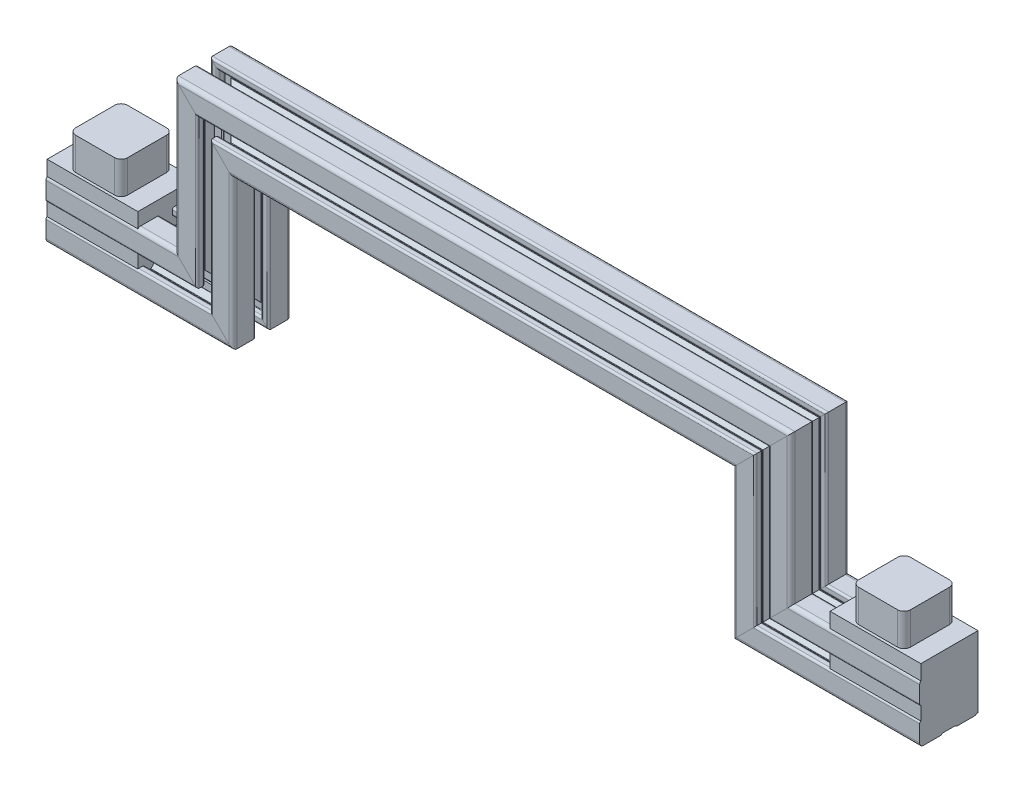
SolidWorks part; units mm, degrees
material "Commercially Pure CP-Ti UNS R50400 (SS)"
ref_plane "Front Plane" through (0, 0, 0) normal (0, 0, 1) x (1, 0, 0)
ref_plane "Top Plane" through (0, 0, 0) normal (0, 1, 0) x (1, 0, 0)
ref_plane "Right Plane" through (0, 0, 0) normal (1, 0, 0) x (0, 0, -1)
sketch "Sketch7" plane through (0, 0, 0) normal (1, 0, 0) x (0, 0, -1)
  line L0 (13.9698, 21.2743) -> (13.5298, 21.2743)
  line L1 (12.0298, 22.7743) -> (12.0298, 23.2743)
  line L2 (13.5298, 24.7743) -> (23.1398, 24.7743)
  line L3 (25.4198, 22.4943) -> (25.4198, 12.8843)
  line L4 (23.9198, 11.3843) -> (23.4198, 11.3843)
  line L5 (21.9198, 12.8843) -> (21.9198, 13.3243)
  line L6 (20.9198, 14.3243) -> (15.3498, 14.3243)
  line L7 (14.9698, 14.7043) -> (14.9698, 20.2743)
  line L8 (21.9589, -6.6897) -> (21.9589, -6.2497)
  line L9 (23.4589, -4.7497) -> (23.9589, -4.7497)
  line L10 (25.4589, -6.2497) -> (25.4589, -15.8597)
  line L11 (23.1789, -18.1397) -> (13.5689, -18.1397)
  line L12 (12.0689, -16.6397) -> (12.0689, -16.1397)
  line L13 (13.5689, -14.6397) -> (14.0089, -14.6397)
  line L14 (15.0089, -13.6397) -> (15.0089, -8.0697)
  line L15 (15.3889, -7.6897) -> (20.9589, -7.6897)
  line L16 (-6.0052, -14.6787) -> (-5.5652, -14.6787)
  line L17 (-4.0652, -16.1787) -> (-4.0652, -16.6787)
  line L18 (-5.5652, -18.1787) -> (-15.1752, -18.1787)
  line L19 (-17.4552, -15.8987) -> (-17.4552, -6.2887)
  line L20 (-15.9552, -4.7887) -> (-15.4552, -4.7887)
  line L21 (-13.9552, -6.2887) -> (-13.9552, -6.7287)
  line L22 (-12.9552, -7.7287) -> (-7.3852, -7.7287)
  line L23 (-7.0052, -8.1087) -> (-7.0052, -13.6787)
  line L24 (1.8289, -2.4886) -> (1.4132, -2.3164)
  line L25 (-1.632, 0.7289) -> (-1.8042, 1.1447)
  line L26 (-1.804, 5.4512) -> (-1.6318, 5.867)
  line L27 (1.4134, 8.9121) -> (1.8292, 9.0843)
  line L28 (6.1358, 9.0842) -> (6.5515, 8.912)
  line L29 (9.5966, 5.8667) -> (9.7688, 5.451)
  line L30 (9.7687, 1.1444) -> (9.5965, 0.7287)
  line L31 (6.5512, -2.3165) -> (6.1355, -2.4887)
  line L32 (-13.9942, 13.2853) -> (-13.9942, 12.8453)
  line L33 (-15.4942, 11.3453) -> (-15.9942, 11.3453)
  line L34 (-17.4942, 12.8453) -> (-17.4942, 22.4553)
  line L35 (-15.2142, 24.7353) -> (-5.6042, 24.7353)
  line L36 (-4.1042, 23.2353) -> (-4.1042, 22.7353)
  line L37 (-5.6042, 21.2353) -> (-6.0442, 21.2353)
  line L38 (-7.0442, 20.2353) -> (-7.0442, 14.6653)
  line L39 (-7.4242, 14.2853) -> (-12.9942, 14.2853)
  line L40 (4.9058, 11.2153) -> (4.0058, 10.7002)
  line L41 (4.0058, 10.7002) -> (3.1058, 11.2153)
  line L42 (3.1058, 11.2153) -> (-2.1975, 11.2153)
  line L43 (-2.4662, 11.3266) -> (-5.9329, 14.7933)
  line L44 (-6.0442, 15.062) -> (-6.0442, 19.3553)
  line L45 (-5.6642, 19.7353) -> (-2.5792, 19.7353)
  line L46 (-1.0592, 21.2553) -> (-1.0592, 24.2153)
  line L47 (-2.5792, 25.7353) -> (-15.4942, 25.7353)
  line L48 (-18.4942, 22.7353) -> (-18.4942, 9.8203)
  line L49 (-16.9742, 8.3003) -> (-14.0142, 8.3003)
  line L50 (-12.4942, 9.8203) -> (-12.4942, 12.9053)
  line L51 (-12.1142, 13.2853) -> (-7.8138, 13.2853)
  line L52 (-7.5451, 13.174) -> (-4.0855, 9.7144)
  line L53 (-3.9742, 9.4457) -> (-3.9742, 4.1353)
  line L54 (-3.9742, 4.1353) -> (-3.4546, 3.2353)
  line L55 (-3.4546, 3.2353) -> (-3.9742, 2.3353)
  line L56 (-3.9742, 2.3353) -> (-3.9742, -2.968)
  line L57 (-4.0855, -3.2367) -> (-7.5522, -6.7034)
  line L58 (-7.8209, -6.8147) -> (-12.1142, -6.8147)
  line L59 (-12.4942, -6.4347) -> (-12.4942, -3.3497)
  line L60 (-14.0142, -1.8297) -> (-16.9742, -1.8297)
  line L61 (-18.4942, -3.3497) -> (-18.4942, -16.2647)
  line L62 (-15.4942, -19.2647) -> (-2.5792, -19.2647)
  line L63 (-1.0592, -17.7447) -> (-1.0592, -14.7847)
  line L64 (-2.5792, -13.2647) -> (-5.6642, -13.2647)
  line L65 (-6.0442, -12.8847) -> (-6.0442, -8.5843)
  line L66 (-5.9329, -8.3156) -> (-2.4733, -4.856)
  line L67 (-2.2046, -4.7447) -> (3.1058, -4.7447)
  line L68 (3.1058, -4.7447) -> (4.0058, -4.2295)
  line L69 (4.0058, -4.2295) -> (4.9058, -4.7447)
  line L70 (4.9058, -4.7447) -> (10.2091, -4.7447)
  line L71 (10.4778, -4.856) -> (13.9445, -8.3227)
  line L72 (14.0558, -8.5914) -> (14.0558, -12.8847)
  line L73 (13.6758, -13.2647) -> (10.5908, -13.2647)
  line L74 (9.0708, -14.7847) -> (9.0708, -17.7447)
  line L75 (10.5908, -19.2647) -> (23.5058, -19.2647)
  line L76 (26.5058, -16.2647) -> (26.5058, -3.3497)
  line L77 (24.9858, -1.8297) -> (22.0258, -1.8297)
  line L78 (20.5058, -3.3497) -> (20.5058, -6.4347)
  line L79 (20.1258, -6.8147) -> (15.8254, -6.8147)
  line L80 (15.5567, -6.7034) -> (12.0971, -3.2438)
  line L81 (11.9858, -2.9751) -> (11.9858, 2.3353)
  line L82 (11.9858, 2.3353) -> (11.4662, 3.2353)
  line L83 (11.4662, 3.2353) -> (11.9858, 4.1353)
  line L84 (11.9858, 4.1353) -> (11.9858, 9.4386)
  line L85 (12.0971, 9.7073) -> (15.5638, 13.174)
  line L86 (15.8325, 13.2853) -> (20.1258, 13.2853)
  line L87 (20.5058, 12.9053) -> (20.5058, 9.8203)
  line L88 (22.0258, 8.3003) -> (24.9858, 8.3003)
  line L89 (26.5058, 9.8203) -> (26.5058, 22.7353)
  line L90 (23.5058, 25.7353) -> (10.5908, 25.7353)
  line L91 (9.0708, 24.2153) -> (9.0708, 21.2553)
  line L92 (10.5908, 19.7353) -> (13.6758, 19.7353)
  line L93 (14.0558, 19.3553) -> (14.0558, 15.0549)
  line L94 (13.9445, 14.7862) -> (10.4849, 11.3266)
  line L95 (10.2162, 11.2153) -> (4.9058, 11.2153)
  arc A0 (14.9698, 20.2743) -> (13.9698, 21.2743) centre (13.9698, 20.2743) ccw
  arc A1 (12.0298, 22.7743) -> (13.5298, 21.2743) centre (13.5298, 22.7743) ccw
  arc A2 (13.5298, 24.7743) -> (12.0298, 23.2743) centre (13.5298, 23.2743) ccw
  arc A3 (25.4198, 22.4943) -> (23.1398, 24.7743) centre (23.1398, 22.4943) ccw
  arc A4 (23.9198, 11.3843) -> (25.4198, 12.8843) centre (23.9198, 12.8843) ccw
  arc A5 (21.9198, 12.8843) -> (23.4198, 11.3843) centre (23.4198, 12.8843) ccw
  arc A6 (21.9198, 13.3243) -> (20.9198, 14.3243) centre (20.9198, 13.3243) ccw
  arc A7 (14.9698, 14.7043) -> (15.3498, 14.3243) centre (15.3498, 14.7043) ccw
  arc A8 (20.9589, -7.6897) -> (21.9589, -6.6897) centre (20.9589, -6.6897) ccw
  arc A9 (23.4589, -4.7497) -> (21.9589, -6.2497) centre (23.4589, -6.2497) ccw
  arc A10 (25.4589, -6.2497) -> (23.9589, -4.7497) centre (23.9589, -6.2497) ccw
  arc A11 (23.1789, -18.1397) -> (25.4589, -15.8597) centre (23.1789, -15.8597) ccw
  arc A12 (12.0689, -16.6397) -> (13.5689, -18.1397) centre (13.5689, -16.6397) ccw
  arc A13 (13.5689, -14.6397) -> (12.0689, -16.1397) centre (13.5689, -16.1397) ccw
  arc A14 (14.0089, -14.6397) -> (15.0089, -13.6397) centre (14.0089, -13.6397) ccw
  arc A15 (15.3889, -7.6897) -> (15.0089, -8.0697) centre (15.3889, -8.0697) ccw
  arc A16 (-7.0052, -13.6787) -> (-6.0052, -14.6787) centre (-6.0052, -13.6787) ccw
  arc A17 (-4.0652, -16.1787) -> (-5.5652, -14.6787) centre (-5.5652, -16.1787) ccw
  arc A18 (-5.5652, -18.1787) -> (-4.0652, -16.6787) centre (-5.5652, -16.6787) ccw
  arc A19 (-17.4552, -15.8987) -> (-15.1752, -18.1787) centre (-15.1752, -15.8987) ccw
  arc A20 (-15.9552, -4.7887) -> (-17.4552, -6.2887) centre (-15.9552, -6.2887) ccw
  arc A21 (-13.9552, -6.2887) -> (-15.4552, -4.7887) centre (-15.4552, -6.2887) ccw
  arc A22 (-13.9552, -6.7287) -> (-12.9552, -7.7287) centre (-12.9552, -6.7287) ccw
  arc A23 (-7.0052, -8.1087) -> (-7.3852, -7.7287) centre (-7.3852, -8.1087) ccw
  arc A24 (1.0363, -0.7421) -> (1.4132, -2.3164) centre (1.7959, -1.3925) ccw
  arc A25 (-0.0577, 0.352) -> (1.0363, -0.7421) centre (3.9823, 3.2978) ccw
  arc A26 (-1.632, 0.7289) -> (-0.0577, 0.352) centre (-0.7081, 1.1116) ccw
  arc A27 (-0.9575, 2.5244) -> (-1.8042, 1.1447) centre (-0.8803, 1.5274) ccw
  arc A28 (-0.9574, 4.0715) -> (-0.9575, 2.5244) centre (3.9823, 3.2978) ccw
  arc A29 (-1.804, 5.4512) -> (-0.9574, 4.0715) centre (-0.8802, 5.0686) ccw
  arc A30 (-0.0575, 6.2439) -> (-1.6318, 5.867) centre (-0.708, 5.4843) ccw
  arc A31 (1.0365, 7.3379) -> (-0.0575, 6.2439) centre (3.9823, 3.2978) ccw
  arc A32 (1.4134, 8.9121) -> (1.0365, 7.3379) centre (1.7961, 7.9882) ccw
  arc A33 (3.2089, 8.2376) -> (1.8292, 9.0843) centre (2.2119, 8.1604) ccw
  arc A34 (4.7561, 8.2376) -> (3.2089, 8.2376) centre (3.9823, 3.2978) ccw
  arc A35 (6.1358, 9.0842) -> (4.7561, 8.2376) centre (5.7531, 8.1603) ccw
  arc A36 (6.9284, 7.3377) -> (6.5515, 8.912) centre (6.1688, 7.9881) ccw
  arc A37 (8.0224, 6.2437) -> (6.9284, 7.3377) centre (3.9823, 3.2978) ccw
  arc A38 (9.5966, 5.8667) -> (8.0224, 6.2437) centre (8.6727, 5.484) ccw
  arc A39 (8.9222, 4.0713) -> (9.7688, 5.451) centre (8.845, 5.0683) ccw
  arc A40 (8.9221, 2.5241) -> (8.9222, 4.0713) centre (3.9823, 3.2978) ccw
  arc A41 (9.7687, 1.1444) -> (8.9221, 2.5241) centre (8.8448, 1.5271) ccw
  arc A42 (8.0222, 0.3518) -> (9.5965, 0.7287) centre (8.6726, 1.1113) ccw
  arc A43 (6.9282, -0.7422) -> (8.0222, 0.3518) centre (3.9823, 3.2978) ccw
  arc A44 (6.5512, -2.3165) -> (6.9282, -0.7422) centre (6.1685, -1.3926) ccw
  arc A45 (4.7558, -1.642) -> (6.1355, -2.4887) centre (5.7528, -1.5648) ccw
  arc A46 (3.2086, -1.642) -> (4.7558, -1.642) centre (3.9823, 3.2978) ccw
  arc A47 (1.8289, -2.4886) -> (3.2086, -1.642) centre (2.2116, -1.5647) ccw
  arc A48 (-12.9942, 14.2853) -> (-13.9942, 13.2853) centre (-12.9942, 13.2853) ccw
  arc A49 (-15.4942, 11.3453) -> (-13.9942, 12.8453) centre (-15.4942, 12.8453) ccw
  arc A50 (-17.4942, 12.8453) -> (-15.9942, 11.3453) centre (-15.9942, 12.8453) ccw
  arc A51 (-15.2142, 24.7353) -> (-17.4942, 22.4553) centre (-15.2142, 22.4553) ccw
  arc A52 (-4.1042, 23.2353) -> (-5.6042, 24.7353) centre (-5.6042, 23.2353) ccw
  arc A53 (-5.6042, 21.2353) -> (-4.1042, 22.7353) centre (-5.6042, 22.7353) ccw
  arc A54 (-6.0442, 21.2353) -> (-7.0442, 20.2353) centre (-6.0442, 20.2353) ccw
  arc A55 (-7.4242, 14.2853) -> (-7.0442, 14.6653) centre (-7.4242, 14.6653) ccw
  arc A56 (-2.4662, 11.3266) -> (-2.1975, 11.2153) centre (-2.1975, 11.5953) ccw
  arc A57 (-6.0442, 15.062) -> (-5.9329, 14.7933) centre (-5.6642, 15.062) ccw
  arc A58 (-5.6642, 19.7353) -> (-6.0442, 19.3553) centre (-5.6642, 19.3553) ccw
  arc A59 (-2.5792, 19.7353) -> (-1.0592, 21.2553) centre (-2.5792, 21.2553) ccw
  arc A60 (-1.0592, 24.2153) -> (-2.5792, 25.7353) centre (-2.5792, 24.2153) ccw
  arc A61 (-15.4942, 25.7353) -> (-18.4942, 22.7353) centre (-15.4942, 22.7353) ccw
  arc A62 (-18.4942, 9.8203) -> (-16.9742, 8.3003) centre (-16.9742, 9.8203) ccw
  arc A63 (-14.0142, 8.3003) -> (-12.4942, 9.8203) centre (-14.0142, 9.8203) ccw
  arc A64 (-12.1142, 13.2853) -> (-12.4942, 12.9053) centre (-12.1142, 12.9053) ccw
  arc A65 (-7.5451, 13.174) -> (-7.8138, 13.2853) centre (-7.8138, 12.9053) ccw
  arc A66 (-3.9742, 9.4457) -> (-4.0855, 9.7144) centre (-4.3542, 9.4457) ccw
  arc A67 (-4.0855, -3.2367) -> (-3.9742, -2.968) centre (-4.3542, -2.968) ccw
  arc A68 (-7.8209, -6.8147) -> (-7.5522, -6.7034) centre (-7.8209, -6.4347) ccw
  arc A69 (-12.4942, -6.4347) -> (-12.1142, -6.8147) centre (-12.1142, -6.4347) ccw
  arc A70 (-12.4942, -3.3497) -> (-14.0142, -1.8297) centre (-14.0142, -3.3497) ccw
  arc A71 (-16.9742, -1.8297) -> (-18.4942, -3.3497) centre (-16.9742, -3.3497) ccw
  arc A72 (-18.4942, -16.2647) -> (-15.4942, -19.2647) centre (-15.4942, -16.2647) ccw
  arc A73 (-2.5792, -19.2647) -> (-1.0592, -17.7447) centre (-2.5792, -17.7447) ccw
  arc A74 (-1.0592, -14.7847) -> (-2.5792, -13.2647) centre (-2.5792, -14.7847) ccw
  arc A75 (-6.0442, -12.8847) -> (-5.6642, -13.2647) centre (-5.6642, -12.8847) ccw
  arc A76 (-5.9329, -8.3156) -> (-6.0442, -8.5843) centre (-5.6642, -8.5843) ccw
  arc A77 (-2.2046, -4.7447) -> (-2.4733, -4.856) centre (-2.2046, -5.1247) ccw
  arc A78 (10.4778, -4.856) -> (10.2091, -4.7447) centre (10.2091, -5.1247) ccw
  arc A79 (14.0558, -8.5914) -> (13.9445, -8.3227) centre (13.6758, -8.5914) ccw
  arc A80 (13.6758, -13.2647) -> (14.0558, -12.8847) centre (13.6758, -12.8847) ccw
  arc A81 (10.5908, -13.2647) -> (9.0708, -14.7847) centre (10.5908, -14.7847) ccw
  arc A82 (9.0708, -17.7447) -> (10.5908, -19.2647) centre (10.5908, -17.7447) ccw
  arc A83 (23.5058, -19.2647) -> (26.5058, -16.2647) centre (23.5058, -16.2647) ccw
  arc A84 (26.5058, -3.3497) -> (24.9858, -1.8297) centre (24.9858, -3.3497) ccw
  arc A85 (22.0258, -1.8297) -> (20.5058, -3.3497) centre (22.0258, -3.3497) ccw
  arc A86 (20.1258, -6.8147) -> (20.5058, -6.4347) centre (20.1258, -6.4347) ccw
  arc A87 (15.5567, -6.7034) -> (15.8254, -6.8147) centre (15.8254, -6.4347) ccw
  arc A88 (11.9858, -2.9751) -> (12.0971, -3.2438) centre (12.3658, -2.9751) ccw
  arc A89 (12.0971, 9.7073) -> (11.9858, 9.4386) centre (12.3658, 9.4386) ccw
  arc A90 (15.8325, 13.2853) -> (15.5638, 13.174) centre (15.8325, 12.9053) ccw
  arc A91 (20.5058, 12.9053) -> (20.1258, 13.2853) centre (20.1258, 12.9053) ccw
  arc A92 (20.5058, 9.8203) -> (22.0258, 8.3003) centre (22.0258, 9.8203) ccw
  arc A93 (24.9858, 8.3003) -> (26.5058, 9.8203) centre (24.9858, 9.8203) ccw
  arc A94 (26.5058, 22.7353) -> (23.5058, 25.7353) centre (23.5058, 22.7353) ccw
  arc A95 (10.5908, 25.7353) -> (9.0708, 24.2153) centre (10.5908, 24.2153) ccw
  arc A96 (9.0708, 21.2553) -> (10.5908, 19.7353) centre (10.5908, 21.2553) ccw
  arc A97 (14.0558, 19.3553) -> (13.6758, 19.7353) centre (13.6758, 19.3553) ccw
  arc A98 (13.9445, 14.7862) -> (14.0558, 15.0549) centre (13.6758, 15.0549) ccw
  arc A99 (10.2162, 11.2153) -> (10.4849, 11.3266) centre (10.2162, 11.5953) ccw
sketch "Sketch1" plane through (0, 0, 0) normal (0, 0, 1) x (1, 0, 0)
  line L0 (0, 0) -> (125, 0)
  line L1 (125, 0) -> (125, 115.0707)
  line L2 (125, 115.0707) -> (337, 115.0707)
  dimension "D1" = 337
  dimension "D2" = 125
sketch "Sketch2" [suppressed] plane through (0, 0, 0) normal (1, 0, 0) x (0, 0, -1)
  line L0 (-33.5, -41) -> (-31.5, -41)
  line L1 (-31.5, -43) -> (-42, -43)
  line L2 (-43, -42) -> (-43, -31.5)
  line L3 (-41, -31.5) -> (-41, -33.5)
  line L4 (-40, -34.5) -> (-34.88, -34.5)
  line L5 (-34.5, -34.88) -> (-34.5, -40)
  line L6 (-16.657, -26.2238) -> (-18.284, -25.188)
  line L7 (-19.8123, -26.7162) -> (-18.7764, -28.3429)
  line L8 (-21.0015, -29.2647) -> (-21.4195, -27.3819)
  line L9 (-23.5808, -27.3818) -> (-23.9986, -29.2645)
  line L10 (-26.2238, -28.343) -> (-25.188, -26.716)
  line L11 (-26.7162, -25.1877) -> (-28.3429, -26.2236)
  line L12 (-29.2647, -23.9985) -> (-27.3819, -23.5805)
  line L13 (-27.3818, -21.4192) -> (-29.2645, -21.0014)
  line L14 (-28.343, -18.7762) -> (-26.716, -19.812)
  line L15 (-25.1877, -18.2838) -> (-26.2236, -16.6571)
  line L16 (-23.9985, -15.7353) -> (-23.5805, -17.6181)
  line L17 (-21.4192, -17.6182) -> (-21.0014, -15.7355)
  line L18 (-18.7762, -16.657) -> (-19.812, -18.284)
  line L19 (-18.2838, -19.8123) -> (-16.6571, -18.7764)
  line L20 (-15.7353, -21.0015) -> (-17.6181, -21.4195)
  line L21 (-17.6182, -23.5808) -> (-15.7355, -23.9986)
  line L22 (41, -33.5) -> (41, -31.5)
  line L23 (43, -31.5) -> (43, -42)
  line L24 (42, -43) -> (31.5, -43)
  line L25 (31.5, -41) -> (33.5, -41)
  line L26 (34.5, -40) -> (34.5, -34.88)
  line L27 (34.88, -34.5) -> (40, -34.5)
  line L28 (26.7162, -19.8123) -> (28.3429, -18.7764)
  line L29 (29.2647, -21.0015) -> (27.3819, -21.4195)
  line L30 (27.3818, -23.5808) -> (29.2645, -23.9986)
  line L31 (28.343, -26.2238) -> (26.716, -25.188)
  line L32 (25.1877, -26.7162) -> (26.2236, -28.3429)
  line L33 (23.9985, -29.2647) -> (23.5805, -27.3819)
  line L34 (21.4192, -27.3818) -> (21.0014, -29.2645)
  line L35 (18.7762, -28.343) -> (19.812, -26.716)
  line L36 (18.2838, -25.1877) -> (16.6571, -26.2236)
  line L37 (15.7353, -23.9985) -> (17.6181, -23.5805)
  line L38 (17.6182, -21.4192) -> (15.7355, -21.0014)
  line L39 (16.657, -18.7762) -> (18.284, -19.812)
  line L40 (19.8123, -18.2838) -> (18.7764, -16.6571)
  line L41 (21.0015, -15.7353) -> (21.4195, -17.6181)
  line L42 (23.5808, -17.6182) -> (23.9986, -15.7355)
  line L43 (26.2238, -16.657) -> (25.188, -18.284)
  line L44 (34.5, 34.88) -> (34.5, 40)
  line L45 (33.5, 41) -> (31.5, 41)
  line L46 (31.5, 43) -> (42, 43)
  line L47 (43, 42) -> (43, 31.5)
  line L48 (41, 31.5) -> (41, 33.5)
  line L49 (40, 34.5) -> (34.88, 34.5)
  line L50 (26.7162, 25.1877) -> (28.3429, 26.2236)
  line L51 (29.2647, 23.9985) -> (27.3819, 23.5805)
  line L52 (27.3818, 21.4192) -> (29.2645, 21.0014)
  line L53 (28.343, 18.7762) -> (26.716, 19.812)
  line L54 (25.1877, 18.2838) -> (26.2236, 16.6571)
  line L55 (23.9985, 15.7353) -> (23.5805, 17.6181)
  line L56 (21.4192, 17.6182) -> (21.0014, 15.7355)
  line L57 (18.7762, 16.657) -> (19.812, 18.284)
  line L58 (18.2838, 19.8123) -> (16.6571, 18.7764)
  line L59 (15.7353, 21.0015) -> (17.6181, 21.4195)
  line L60 (17.6182, 23.5808) -> (15.7355, 23.9986)
  line L61 (16.657, 26.2238) -> (18.284, 25.188)
  line L62 (19.8123, 26.7162) -> (18.7764, 28.3429)
  line L63 (21.0015, 29.2647) -> (21.4195, 27.3819)
  line L64 (23.5808, 27.3818) -> (23.9986, 29.2645)
  line L65 (26.2238, 28.343) -> (25.188, 26.716)
  line L66 (-41, 33.5) -> (-41, 31.5)
  line L67 (-43, 31.5) -> (-43, 42)
  line L68 (-42, 43) -> (-31.5, 43)
  line L69 (-31.5, 41) -> (-33.5, 41)
  line L70 (-34.5, 40) -> (-34.5, 34.88)
  line L71 (-34.88, 34.5) -> (-40, 34.5)
  line L72 (-16.657, 18.7762) -> (-18.284, 19.812)
  line L73 (-19.8123, 18.2838) -> (-18.7764, 16.6571)
  line L74 (-21.0015, 15.7353) -> (-21.4195, 17.6181)
  line L75 (-23.5808, 17.6182) -> (-23.9986, 15.7355)
  line L76 (-26.2238, 16.657) -> (-25.188, 18.284)
  line L77 (-26.7162, 19.8123) -> (-28.3429, 18.7764)
  line L78 (-29.2647, 21.0015) -> (-27.3819, 21.4195)
  line L79 (-27.3818, 23.5808) -> (-29.2645, 23.9986)
  line L80 (-28.343, 26.2238) -> (-26.716, 25.188)
  line L81 (-25.1877, 26.7162) -> (-26.2236, 28.3429)
  line L82 (-23.9985, 29.2647) -> (-23.5805, 27.3819)
  line L83 (-21.4192, 27.3818) -> (-21.0014, 29.2645)
  line L84 (-18.7762, 28.343) -> (-19.812, 26.716)
  line L85 (-18.2838, 25.1877) -> (-16.6571, 26.2236)
  line L86 (-15.7353, 23.9985) -> (-17.6181, 23.5805)
  line L87 (-17.6182, 21.4192) -> (-15.7355, 21.0014)
  line L88 (39, -10.16) -> (33.3774, -10.16)
  line L89 (31.9632, -10.7458) -> (29.8203, -12.8887)
  line L90 (29.5516, -13) -> (23.4, -13)
  line L91 (23.4, -13) -> (22.5, -13.5151)
  line L92 (22.5, -13.5151) -> (21.6, -13)
  line L93 (21.6, -13) -> (15, -13)
  line L94 (13, -15) -> (13, -21.6)
  line L95 (13, -21.6) -> (13.5196, -22.5)
  line L96 (13.5196, -22.5) -> (13, -23.4)
  line L97 (13, -23.4) -> (13, -29.5516)
  line L98 (12.8887, -29.8203) -> (11.3787, -31.3303)
  line L99 (10.5, -33.4516) -> (10.5, -40)
  line L100 (11.5, -41) -> (13.5, -41)
  line L101 (13.5, -43) -> (-13.5, -43)
  line L102 (-13.5, -41) -> (-11.5, -41)
  line L103 (-10.5, -40) -> (-10.5, -33.4516)
  line L104 (-11.3787, -31.3303) -> (-12.8887, -29.8203)
  line L105 (-13, -29.5516) -> (-13, -23.4)
  line L106 (-13, -23.4) -> (-13.5196, -22.5)
  line L107 (-13.5196, -22.5) -> (-13, -21.6)
  line L108 (-13, -21.6) -> (-13, -15)
  line L109 (-15, -13) -> (-21.6, -13)
  line L110 (-21.6, -13) -> (-22.5, -13.5151)
  line L111 (-22.5, -13.5151) -> (-23.4, -13)
  line L112 (-23.4, -13) -> (-29.5516, -13)
  line L113 (-29.8203, -12.8887) -> (-31.9632, -10.7458)
  line L114 (-33.3774, -10.16) -> (-39, -10.16)
  line L115 (-41, -12.16) -> (-41, -13.5)
  line L116 (-43, -13.5) -> (-43, 13.5)
  line L117 (-41, 13.5) -> (-41, 12.16)
  line L118 (-39, 10.16) -> (-33.3774, 10.16)
  line L119 (-31.9632, 10.7458) -> (-29.8203, 12.8887)
  line L120 (-29.5516, 13) -> (-23.4, 13)
  line L121 (-23.4, 13) -> (-22.5, 13.5151)
  line L122 (-22.5, 13.5151) -> (-21.6, 13)
  line L123 (-21.6, 13) -> (-15, 13)
  line L124 (-13, 15) -> (-13, 21.6)
  line L125 (-13, 21.6) -> (-13.5196, 22.5)
  line L126 (-13.5196, 22.5) -> (-13, 23.4)
  line L127 (-13, 23.4) -> (-13, 29.5516)
  line L128 (-12.8887, 29.8203) -> (-11.3787, 31.3303)
  line L129 (-10.5, 33.4516) -> (-10.5, 40)
  line L130 (-11.5, 41) -> (-13.5, 41)
  line L131 (-13.5, 43) -> (13.5, 43)
  line L132 (13.5, 41) -> (11.5, 41)
  line L133 (10.5, 40) -> (10.5, 33.4516)
  line L134 (11.3787, 31.3303) -> (12.8887, 29.8203)
  line L135 (13, 29.5516) -> (13, 23.4)
  line L136 (13, 23.4) -> (13.5196, 22.5)
  line L137 (13.5196, 22.5) -> (13, 21.6)
  line L138 (13, 21.6) -> (13, 15)
  line L139 (15, 13) -> (21.6, 13)
  line L140 (21.6, 13) -> (22.5, 13.5151)
  line L141 (22.5, 13.5151) -> (23.4, 13)
  line L142 (23.4, 13) -> (29.5516, 13)
  line L143 (29.8203, 12.8887) -> (31.9581, 10.7509)
  line L144 (33.3723, 10.1651) -> (39, 10.1651)
  line L145 (41, 12.1651) -> (41, 13.5)
  line L146 (43, 13.5) -> (43, -13.5)
  line L147 (41, -13.5) -> (41, -12.16)
  line L148 (45, -15.915) -> (45, 15.915)
  line L149 (43.48, 17.435) -> (40.52, 17.435)
  line L150 (39, 15.915) -> (39, 13.45)
  line L151 (38, 12.45) -> (34.9984, 12.45)
  line L152 (34.7297, 12.5613) -> (32.1113, 15.1797)
  line L153 (32, 15.4484) -> (32, 21.6)
  line L154 (32, 21.6) -> (31.4804, 22.5)
  line L155 (31.4804, 22.5) -> (32, 23.4)
  line L156 (32, 23.4) -> (32, 29.5516)
  line L157 (32.1113, 29.8203) -> (34.7297, 32.4387)
  line L158 (34.9984, 32.55) -> (38, 32.55)
  line L159 (39, 31.55) -> (39, 29.085)
  line L160 (40.52, 27.565) -> (43.48, 27.565)
  line L161 (45, 29.085) -> (45, 42)
  line L162 (42, 45) -> (29.085, 45)
  line L163 (27.565, 43.48) -> (27.565, 40.52)
  line L164 (29.085, 39) -> (31.55, 39)
  line L165 (32.55, 38) -> (32.55, 34.9984)
  line L166 (32.4387, 34.7297) -> (29.8203, 32.1113)
  line L167 (29.5516, 32) -> (23.4, 32)
  line L168 (23.4, 32) -> (22.5, 31.4849)
  line L169 (22.5, 31.4849) -> (21.6, 32)
  line L170 (21.6, 32) -> (15.4484, 32)
  line L171 (15.1797, 32.1113) -> (12.5613, 34.7297)
  line L172 (12.45, 34.9984) -> (12.45, 38)
  line L173 (13.45, 39) -> (15.915, 39)
  line L174 (17.435, 40.52) -> (17.435, 43.48)
  line L175 (15.915, 45) -> (-15.915, 45)
  line L176 (-17.435, 43.48) -> (-17.435, 40.52)
  line L177 (-15.915, 39) -> (-13.45, 39)
  line L178 (-12.45, 38) -> (-12.45, 34.9984)
  line L179 (-12.5613, 34.7297) -> (-15.1797, 32.1113)
  line L180 (-15.4484, 32) -> (-21.6, 32)
  line L181 (-21.6, 32) -> (-22.5, 31.4849)
  line L182 (-22.5, 31.4849) -> (-23.4, 32)
  line L183 (-23.4, 32) -> (-29.5516, 32)
  line L184 (-29.8203, 32.1113) -> (-32.4387, 34.7297)
  line L185 (-32.55, 34.9984) -> (-32.55, 38)
  line L186 (-31.55, 39) -> (-29.085, 39)
  line L187 (-27.565, 40.52) -> (-27.565, 43.48)
  line L188 (-29.085, 45) -> (-42, 45)
  line L189 (-45, 42) -> (-45, 29.085)
  line L190 (-43.48, 27.565) -> (-40.52, 27.565)
  line L191 (-39, 29.085) -> (-39, 31.55)
  line L192 (-38, 32.55) -> (-34.9984, 32.55)
  line L193 (-34.7297, 32.4387) -> (-32.1113, 29.8203)
  line L194 (-32, 29.5516) -> (-32, 23.4)
  line L195 (-32, 23.4) -> (-31.4804, 22.5)
  line L196 (-31.4804, 22.5) -> (-32, 21.6)
  line L197 (-32, 21.6) -> (-32, 15.4484)
  line L198 (-32.1113, 15.1797) -> (-34.7297, 12.5613)
  line L199 (-34.9984, 12.45) -> (-38, 12.45)
  line L200 (-39, 13.45) -> (-39, 15.915)
  line L201 (-40.52, 17.435) -> (-43.48, 17.435)
  line L202 (-45, 15.915) -> (-45, -15.915)
  line L203 (-43.48, -17.435) -> (-40.52, -17.435)
  line L204 (-39, -15.915) -> (-39, -13.45)
  line L205 (-38, -12.45) -> (-34.9984, -12.45)
  line L206 (-34.7297, -12.5613) -> (-32.1113, -15.1797)
  line L207 (-32, -15.4484) -> (-32, -21.6)
  line L208 (-32, -21.6) -> (-31.4804, -22.5)
  line L209 (-31.4804, -22.5) -> (-32, -23.4)
  line L210 (-32, -23.4) -> (-32, -29.5516)
  line L211 (-32.1113, -29.8203) -> (-34.7297, -32.4387)
  line L212 (-34.9984, -32.55) -> (-38, -32.55)
  line L213 (-39, -31.55) -> (-39, -29.085)
  line L214 (-40.52, -27.565) -> (-43.48, -27.565)
  line L215 (-45, -29.085) -> (-45, -42)
  line L216 (-42, -45) -> (-29.085, -45)
  line L217 (-27.565, -43.48) -> (-27.565, -40.52)
  line L218 (-29.085, -39) -> (-31.55, -39)
  line L219 (-32.55, -38) -> (-32.55, -34.9984)
  line L220 (-32.4387, -34.7297) -> (-29.8203, -32.1113)
  line L221 (-29.5516, -32) -> (-23.4, -32)
  line L222 (-23.4, -32) -> (-22.5, -31.4849)
  line L223 (-22.5, -31.4849) -> (-21.6, -32)
  line L224 (-21.6, -32) -> (-15.4484, -32)
  line L225 (-15.1797, -32.1113) -> (-12.5613, -34.7297)
  line L226 (-12.45, -34.9984) -> (-12.45, -38)
  line L227 (-13.45, -39) -> (-15.915, -39)
  line L228 (-17.435, -40.52) -> (-17.435, -43.48)
  line L229 (-15.915, -45) -> (15.915, -45)
  line L230 (17.435, -43.48) -> (17.435, -40.52)
  line L231 (15.915, -39) -> (13.45, -39)
  line L232 (12.45, -38) -> (12.45, -34.9984)
  line L233 (12.5613, -34.7297) -> (15.1797, -32.1113)
  line L234 (15.4484, -32) -> (21.6, -32)
  line L235 (21.6, -32) -> (22.5, -31.4849)
  line L236 (22.5, -31.4849) -> (23.4, -32)
  line L237 (23.4, -32) -> (29.5516, -32)
  line L238 (29.8203, -32.1113) -> (32.4387, -34.7297)
  line L239 (32.55, -34.9984) -> (32.55, -38)
  line L240 (31.55, -39) -> (29.085, -39)
  line L241 (27.565, -40.52) -> (27.565, -43.48)
  line L242 (29.085, -45) -> (42, -45)
  line L243 (45, -42) -> (45, -29.085)
  line L244 (43.48, -27.565) -> (40.52, -27.565)
  line L245 (39, -29.085) -> (39, -31.55)
  line L246 (38, -32.55) -> (34.9984, -32.55)
  line L247 (34.7297, -32.4387) -> (32.1113, -29.8203)
  line L248 (32, -29.5516) -> (32, -23.4)
  line L249 (32, -23.4) -> (31.4804, -22.5)
  line L250 (31.4804, -22.5) -> (32, -21.6)
  line L251 (32, -21.6) -> (32, -15.4484)
  line L252 (32.1113, -15.1797) -> (34.7297, -12.5613)
  line L253 (34.9984, -12.45) -> (38, -12.45)
  line L254 (39, -13.45) -> (39, -15.915)
  line L255 (40.52, -17.435) -> (43.48, -17.435)
  arc A0 (-34.5, -40) -> (-33.5, -41) centre (-33.5, -40) ccw
  arc A1 (-31.5, -43) -> (-31.5, -41) centre (-31.5, -42) ccw
  arc A2 (-43, -42) -> (-42, -43) centre (-42, -42) ccw
  arc A3 (-41, -31.5) -> (-43, -31.5) centre (-42, -31.5) ccw
  arc A4 (-41, -33.5) -> (-40, -34.5) centre (-40, -33.5) ccw
  arc A5 (-34.5, -34.88) -> (-34.88, -34.5) centre (-34.88, -34.88) ccw
  arc A6 (-15.2086, -25.7917) -> (-15.0167, -25.3284) centre (-22.5, -22.5) ccw
  arc A7 (-16.657, -26.2238) -> (-15.2086, -25.7917) centre (-16.12, -25.3802) ccw
  arc A8 (-19.8123, -26.7162) -> (-18.284, -25.188) centre (-22.5, -22.5) ccw
  arc A9 (-19.2085, -29.7915) -> (-18.7764, -28.3429) centre (-19.6199, -28.8801) ccw
  arc A10 (-19.6717, -29.9834) -> (-19.2085, -29.7915) centre (-22.5, -22.5) ccw
  arc A11 (-21.0015, -29.2647) -> (-19.6717, -29.9834) centre (-20.0253, -29.048) ccw
  arc A12 (-23.5808, -27.3818) -> (-21.4195, -27.3819) centre (-22.5, -22.5) ccw
  arc A13 (-25.3284, -29.9833) -> (-23.9986, -29.2645) centre (-24.9749, -29.0479) ccw
  arc A14 (-25.7917, -29.7914) -> (-25.3284, -29.9833) centre (-22.5, -22.5) ccw
  arc A15 (-26.2238, -28.343) -> (-25.7917, -29.7914) centre (-25.3802, -28.88) ccw
  arc A16 (-26.7162, -25.1877) -> (-25.188, -26.716) centre (-22.5, -22.5) ccw
  arc A17 (-29.7915, -25.7915) -> (-28.3429, -26.2236) centre (-28.8801, -25.3801) ccw
  arc A18 (-29.9834, -25.3283) -> (-29.7915, -25.7915) centre (-22.5, -22.5) ccw
  arc A19 (-29.2647, -23.9985) -> (-29.9834, -25.3283) centre (-29.048, -24.9747) ccw
  arc A20 (-27.3818, -21.4192) -> (-27.3819, -23.5805) centre (-22.5, -22.5) ccw
  arc A21 (-29.9833, -19.6716) -> (-29.2645, -21.0014) centre (-29.0479, -20.0251) ccw
  arc A22 (-29.7914, -19.2083) -> (-29.9833, -19.6716) centre (-22.5, -22.5) ccw
  arc A23 (-28.343, -18.7762) -> (-29.7914, -19.2083) centre (-28.88, -19.6198) ccw
  arc A24 (-25.1877, -18.2838) -> (-26.716, -19.812) centre (-22.5, -22.5) ccw
  arc A25 (-25.7915, -15.2085) -> (-26.2236, -16.6571) centre (-25.3801, -16.1199) ccw
  arc A26 (-25.3283, -15.0166) -> (-25.7915, -15.2085) centre (-22.5, -22.5) ccw
  arc A27 (-23.9985, -15.7353) -> (-25.3283, -15.0166) centre (-24.9747, -15.952) ccw
  arc A28 (-21.4192, -17.6182) -> (-23.5805, -17.6181) centre (-22.5, -22.5) ccw
  arc A29 (-19.6716, -15.0167) -> (-21.0014, -15.7355) centre (-20.0251, -15.9521) ccw
  arc A30 (-19.2083, -15.2086) -> (-19.6716, -15.0167) centre (-22.5, -22.5) ccw
  arc A31 (-18.7762, -16.657) -> (-19.2083, -15.2086) centre (-19.6198, -16.12) ccw
  arc A32 (-18.2838, -19.8123) -> (-19.812, -18.284) centre (-22.5, -22.5) ccw
  arc A33 (-15.2085, -19.2085) -> (-16.6571, -18.7764) centre (-16.1199, -19.6199) ccw
  arc A34 (-15.0166, -19.6717) -> (-15.2085, -19.2085) centre (-22.5, -22.5) ccw
  arc A35 (-15.7353, -21.0015) -> (-15.0166, -19.6717) centre (-15.952, -20.0253) ccw
  arc A36 (-17.6182, -23.5808) -> (-17.6181, -21.4195) centre (-22.5, -22.5) ccw
  arc A37 (-15.0167, -25.3284) -> (-15.7355, -23.9986) centre (-15.9521, -24.9749) ccw
  arc A38 (40, -34.5) -> (41, -33.5) centre (40, -33.5) ccw
  arc A39 (43, -31.5) -> (41, -31.5) centre (42, -31.5) ccw
  arc A40 (42, -43) -> (43, -42) centre (42, -42) ccw
  arc A41 (31.5, -41) -> (31.5, -43) centre (31.5, -42) ccw
  arc A42 (33.5, -41) -> (34.5, -40) centre (33.5, -40) ccw
  arc A43 (34.88, -34.5) -> (34.5, -34.88) centre (34.88, -34.88) ccw
  arc A44 (26.7162, -19.8123) -> (25.188, -18.284) centre (22.5, -22.5) ccw
  arc A45 (29.7915, -19.2085) -> (28.3429, -18.7764) centre (28.8801, -19.6199) ccw
  arc A46 (29.9834, -19.6717) -> (29.7915, -19.2085) centre (22.5, -22.5) ccw
  arc A47 (29.2647, -21.0015) -> (29.9834, -19.6717) centre (29.048, -20.0253) ccw
  arc A48 (27.3818, -23.5808) -> (27.3819, -21.4195) centre (22.5, -22.5) ccw
  arc A49 (29.9833, -25.3284) -> (29.2645, -23.9986) centre (29.0479, -24.9749) ccw
  arc A50 (29.7914, -25.7917) -> (29.9833, -25.3284) centre (22.5, -22.5) ccw
  arc A51 (28.343, -26.2238) -> (29.7914, -25.7917) centre (28.88, -25.3802) ccw
  arc A52 (25.1877, -26.7162) -> (26.716, -25.188) centre (22.5, -22.5) ccw
  arc A53 (25.7915, -29.7915) -> (26.2236, -28.3429) centre (25.3801, -28.8801) ccw
  arc A54 (25.3283, -29.9834) -> (25.7915, -29.7915) centre (22.5, -22.5) ccw
  arc A55 (23.9985, -29.2647) -> (25.3283, -29.9834) centre (24.9747, -29.048) ccw
  arc A56 (21.4192, -27.3818) -> (23.5805, -27.3819) centre (22.5, -22.5) ccw
  arc A57 (19.6716, -29.9833) -> (21.0014, -29.2645) centre (20.0251, -29.0479) ccw
  arc A58 (19.2083, -29.7914) -> (19.6716, -29.9833) centre (22.5, -22.5) ccw
  arc A59 (18.7762, -28.343) -> (19.2083, -29.7914) centre (19.6198, -28.88) ccw
  arc A60 (18.2838, -25.1877) -> (19.812, -26.716) centre (22.5, -22.5) ccw
  arc A61 (15.2085, -25.7915) -> (16.6571, -26.2236) centre (16.1199, -25.3801) ccw
  arc A62 (15.0166, -25.3283) -> (15.2085, -25.7915) centre (22.5, -22.5) ccw
  arc A63 (15.7353, -23.9985) -> (15.0166, -25.3283) centre (15.952, -24.9747) ccw
  arc A64 (17.6182, -21.4192) -> (17.6181, -23.5805) centre (22.5, -22.5) ccw
  arc A65 (15.0167, -19.6716) -> (15.7355, -21.0014) centre (15.9521, -20.0251) ccw
  arc A66 (15.2086, -19.2083) -> (15.0167, -19.6716) centre (22.5, -22.5) ccw
  arc A67 (16.657, -18.7762) -> (15.2086, -19.2083) centre (16.12, -19.6198) ccw
  arc A68 (19.8123, -18.2838) -> (18.284, -19.812) centre (22.5, -22.5) ccw
  arc A69 (19.2085, -15.2085) -> (18.7764, -16.6571) centre (19.6199, -16.1199) ccw
  arc A70 (19.6717, -15.0166) -> (19.2085, -15.2085) centre (22.5, -22.5) ccw
  arc A71 (21.0015, -15.7353) -> (19.6717, -15.0166) centre (20.0253, -15.952) ccw
  arc A72 (23.5808, -17.6182) -> (21.4195, -17.6181) centre (22.5, -22.5) ccw
  arc A73 (25.3284, -15.0167) -> (23.9986, -15.7355) centre (24.9749, -15.9521) ccw
  arc A74 (25.7917, -15.2086) -> (25.3284, -15.0167) centre (22.5, -22.5) ccw
  arc A75 (26.2238, -16.657) -> (25.7917, -15.2086) centre (25.3802, -16.12) ccw
  arc A76 (34.5, 34.88) -> (34.88, 34.5) centre (34.88, 34.88) ccw
  arc A77 (34.5, 40) -> (33.5, 41) centre (33.5, 40) ccw
  arc A78 (31.5, 43) -> (31.5, 41) centre (31.5, 42) ccw
  arc A79 (43, 42) -> (42, 43) centre (42, 42) ccw
  arc A80 (41, 31.5) -> (43, 31.5) centre (42, 31.5) ccw
  arc A81 (41, 33.5) -> (40, 34.5) centre (40, 33.5) ccw
  arc A82 (26.7162, 25.1877) -> (25.188, 26.716) centre (22.5, 22.5) ccw
  arc A83 (29.7915, 25.7915) -> (28.3429, 26.2236) centre (28.8801, 25.3801) ccw
  arc A84 (29.9834, 25.3283) -> (29.7915, 25.7915) centre (22.5, 22.5) ccw
  arc A85 (29.2647, 23.9985) -> (29.9834, 25.3283) centre (29.048, 24.9747) ccw
  arc A86 (27.3818, 21.4192) -> (27.3819, 23.5805) centre (22.5, 22.5) ccw
  arc A87 (29.9833, 19.6716) -> (29.2645, 21.0014) centre (29.0479, 20.0251) ccw
  arc A88 (29.7914, 19.2083) -> (29.9833, 19.6716) centre (22.5, 22.5) ccw
  arc A89 (28.343, 18.7762) -> (29.7914, 19.2083) centre (28.88, 19.6198) ccw
  arc A90 (25.1877, 18.2838) -> (26.716, 19.812) centre (22.5, 22.5) ccw
  arc A91 (25.7915, 15.2085) -> (26.2236, 16.6571) centre (25.3801, 16.1199) ccw
  arc A92 (25.3283, 15.0166) -> (25.7915, 15.2085) centre (22.5, 22.5) ccw
  arc A93 (23.9985, 15.7353) -> (25.3283, 15.0166) centre (24.9747, 15.952) ccw
  arc A94 (21.4192, 17.6182) -> (23.5805, 17.6181) centre (22.5, 22.5) ccw
  arc A95 (19.6716, 15.0167) -> (21.0014, 15.7355) centre (20.0251, 15.9521) ccw
  arc A96 (19.2083, 15.2086) -> (19.6716, 15.0167) centre (22.5, 22.5) ccw
  arc A97 (18.7762, 16.657) -> (19.2083, 15.2086) centre (19.6198, 16.12) ccw
  arc A98 (18.2838, 19.8123) -> (19.812, 18.284) centre (22.5, 22.5) ccw
  arc A99 (15.2085, 19.2085) -> (16.6571, 18.7764) centre (16.1199, 19.6199) ccw
  arc A100 (15.0166, 19.6717) -> (15.2085, 19.2085) centre (22.5, 22.5) ccw
  arc A101 (15.7353, 21.0015) -> (15.0166, 19.6717) centre (15.952, 20.0253) ccw
  arc A102 (17.6182, 23.5808) -> (17.6181, 21.4195) centre (22.5, 22.5) ccw
  arc A103 (15.0167, 25.3284) -> (15.7355, 23.9986) centre (15.9521, 24.9749) ccw
  arc A104 (15.2086, 25.7917) -> (15.0167, 25.3284) centre (22.5, 22.5) ccw
  arc A105 (16.657, 26.2238) -> (15.2086, 25.7917) centre (16.12, 25.3802) ccw
  arc A106 (19.8123, 26.7162) -> (18.284, 25.188) centre (22.5, 22.5) ccw
  arc A107 (19.2085, 29.7915) -> (18.7764, 28.3429) centre (19.6199, 28.8801) ccw
  arc A108 (19.6717, 29.9834) -> (19.2085, 29.7915) centre (22.5, 22.5) ccw
  arc A109 (21.0015, 29.2647) -> (19.6717, 29.9834) centre (20.0253, 29.048) ccw
  arc A110 (23.5808, 27.3818) -> (21.4195, 27.3819) centre (22.5, 22.5) ccw
  arc A111 (25.3284, 29.9833) -> (23.9986, 29.2645) centre (24.9749, 29.0479) ccw
  arc A112 (25.7917, 29.7914) -> (25.3284, 29.9833) centre (22.5, 22.5) ccw
  arc A113 (26.2238, 28.343) -> (25.7917, 29.7914) centre (25.3802, 28.88) ccw
  arc A114 (-40, 34.5) -> (-41, 33.5) centre (-40, 33.5) ccw
  arc A115 (-43, 31.5) -> (-41, 31.5) centre (-42, 31.5) ccw
  arc A116 (-42, 43) -> (-43, 42) centre (-42, 42) ccw
  arc A117 (-31.5, 41) -> (-31.5, 43) centre (-31.5, 42) ccw
  arc A118 (-33.5, 41) -> (-34.5, 40) centre (-33.5, 40) ccw
  arc A119 (-34.88, 34.5) -> (-34.5, 34.88) centre (-34.88, 34.88) ccw
  arc A120 (-15.2086, 19.2083) -> (-15.0167, 19.6716) centre (-22.5, 22.5) ccw
  arc A121 (-16.657, 18.7762) -> (-15.2086, 19.2083) centre (-16.12, 19.6198) ccw
  arc A122 (-19.8123, 18.2838) -> (-18.284, 19.812) centre (-22.5, 22.5) ccw
  arc A123 (-19.2085, 15.2085) -> (-18.7764, 16.6571) centre (-19.6199, 16.1199) ccw
  arc A124 (-19.6717, 15.0166) -> (-19.2085, 15.2085) centre (-22.5, 22.5) ccw
  arc A125 (-21.0015, 15.7353) -> (-19.6717, 15.0166) centre (-20.0253, 15.952) ccw
  arc A126 (-23.5808, 17.6182) -> (-21.4195, 17.6181) centre (-22.5, 22.5) ccw
  arc A127 (-25.3284, 15.0167) -> (-23.9986, 15.7355) centre (-24.9749, 15.9521) ccw
  arc A128 (-25.7917, 15.2086) -> (-25.3284, 15.0167) centre (-22.5, 22.5) ccw
  arc A129 (-26.2238, 16.657) -> (-25.7917, 15.2086) centre (-25.3802, 16.12) ccw
  arc A130 (-26.7162, 19.8123) -> (-25.188, 18.284) centre (-22.5, 22.5) ccw
  arc A131 (-29.7915, 19.2085) -> (-28.3429, 18.7764) centre (-28.8801, 19.6199) ccw
  arc A132 (-29.9834, 19.6717) -> (-29.7915, 19.2085) centre (-22.5, 22.5) ccw
  arc A133 (-29.2647, 21.0015) -> (-29.9834, 19.6717) centre (-29.048, 20.0253) ccw
  arc A134 (-27.3818, 23.5808) -> (-27.3819, 21.4195) centre (-22.5, 22.5) ccw
  arc A135 (-29.9833, 25.3284) -> (-29.2645, 23.9986) centre (-29.0479, 24.9749) ccw
  arc A136 (-29.7914, 25.7917) -> (-29.9833, 25.3284) centre (-22.5, 22.5) ccw
  arc A137 (-28.343, 26.2238) -> (-29.7914, 25.7917) centre (-28.88, 25.3802) ccw
  arc A138 (-25.1877, 26.7162) -> (-26.716, 25.188) centre (-22.5, 22.5) ccw
  arc A139 (-25.7915, 29.7915) -> (-26.2236, 28.3429) centre (-25.3801, 28.8801) ccw
  arc A140 (-25.3283, 29.9834) -> (-25.7915, 29.7915) centre (-22.5, 22.5) ccw
  arc A141 (-23.9985, 29.2647) -> (-25.3283, 29.9834) centre (-24.9747, 29.048) ccw
  arc A142 (-21.4192, 27.3818) -> (-23.5805, 27.3819) centre (-22.5, 22.5) ccw
  arc A143 (-19.6716, 29.9833) -> (-21.0014, 29.2645) centre (-20.0251, 29.0479) ccw
  arc A144 (-19.2083, 29.7914) -> (-19.6716, 29.9833) centre (-22.5, 22.5) ccw
  arc A145 (-18.7762, 28.343) -> (-19.2083, 29.7914) centre (-19.6198, 28.88) ccw
  arc A146 (-18.2838, 25.1877) -> (-19.812, 26.716) centre (-22.5, 22.5) ccw
  arc A147 (-15.2085, 25.7915) -> (-16.6571, 26.2236) centre (-16.1199, 25.3801) ccw
  arc A148 (-15.0166, 25.3283) -> (-15.2085, 25.7915) centre (-22.5, 22.5) ccw
  arc A149 (-15.7353, 23.9985) -> (-15.0166, 25.3283) centre (-15.952, 24.9747) ccw
  arc A150 (-17.6182, 21.4192) -> (-17.6181, 23.5805) centre (-22.5, 22.5) ccw
  arc A151 (-15.0167, 19.6716) -> (-15.7355, 21.0014) centre (-15.9521, 20.0251) ccw
  arc A152 (41, -12.16) -> (39, -10.16) centre (39, -12.16) ccw
  arc A153 (33.3774, -10.16) -> (31.9632, -10.7458) centre (33.3774, -12.16) ccw
  arc A154 (29.5516, -13) -> (29.8203, -12.8887) centre (29.5516, -12.62) ccw
  arc A155 (15, -13) -> (13, -15) centre (15, -15) ccw
  arc A156 (12.8887, -29.8203) -> (13, -29.5516) centre (12.62, -29.5516) ccw
  arc A157 (11.3787, -31.3303) -> (10.5, -33.4516) centre (13.5, -33.4516) ccw
  arc A158 (10.5, -40) -> (11.5, -41) centre (11.5, -40) ccw
  arc A159 (13.5, -43) -> (13.5, -41) centre (13.5, -42) ccw
  arc A160 (-13.5, -41) -> (-13.5, -43) centre (-13.5, -42) ccw
  arc A161 (-11.5, -41) -> (-10.5, -40) centre (-11.5, -40) ccw
  arc A162 (-10.5, -33.4516) -> (-11.3787, -31.3303) centre (-13.5, -33.4516) ccw
  arc A163 (-13, -29.5516) -> (-12.8887, -29.8203) centre (-12.62, -29.5516) ccw
  arc A164 (-13, -15) -> (-15, -13) centre (-15, -15) ccw
  arc A165 (-29.8203, -12.8887) -> (-29.5516, -13) centre (-29.5516, -12.62) ccw
  arc A166 (-31.9632, -10.7458) -> (-33.3774, -10.16) centre (-33.3774, -12.16) ccw
  arc A167 (-39, -10.16) -> (-41, -12.16) centre (-39, -12.16) ccw
  arc A168 (-43, -13.5) -> (-41, -13.5) centre (-42, -13.5) ccw
  arc A169 (-41, 13.5) -> (-43, 13.5) centre (-42, 13.5) ccw
  arc A170 (-41, 12.16) -> (-39, 10.16) centre (-39, 12.16) ccw
  arc A171 (-33.3774, 10.16) -> (-31.9632, 10.7458) centre (-33.3774, 12.16) ccw
  arc A172 (-29.5516, 13) -> (-29.8203, 12.8887) centre (-29.5516, 12.62) ccw
  arc A173 (-15, 13) -> (-13, 15) centre (-15, 15) ccw
  arc A174 (-12.8887, 29.8203) -> (-13, 29.5516) centre (-12.62, 29.5516) ccw
  arc A175 (-11.3787, 31.3303) -> (-10.5, 33.4516) centre (-13.5, 33.4516) ccw
  arc A176 (-10.5, 40) -> (-11.5, 41) centre (-11.5, 40) ccw
  arc A177 (-13.5, 43) -> (-13.5, 41) centre (-13.5, 42) ccw
  arc A178 (13.5, 41) -> (13.5, 43) centre (13.5, 42) ccw
  arc A179 (11.5, 41) -> (10.5, 40) centre (11.5, 40) ccw
  arc A180 (10.5, 33.4516) -> (11.3787, 31.3303) centre (13.5, 33.4516) ccw
  arc A181 (13, 29.5516) -> (12.8887, 29.8203) centre (12.62, 29.5516) ccw
  arc A182 (13, 15) -> (15, 13) centre (15, 15) ccw
  arc A183 (29.8203, 12.8887) -> (29.5516, 13) centre (29.5516, 12.62) ccw
  arc A184 (31.9581, 10.7509) -> (33.3723, 10.1651) centre (33.3723, 12.1651) ccw
  arc A185 (39, 10.1651) -> (41, 12.1651) centre (39, 12.1651) ccw
  arc A186 (43, 13.5) -> (41, 13.5) centre (42, 13.5) ccw
  arc A187 (41, -13.5) -> (43, -13.5) centre (42, -13.5) ccw
  arc A188 (45, 15.915) -> (43.48, 17.435) centre (43.48, 15.915) ccw
  arc A189 (40.52, 17.435) -> (39, 15.915) centre (40.52, 15.915) ccw
  arc A190 (38, 12.45) -> (39, 13.45) centre (38, 13.45) ccw
  arc A191 (34.7297, 12.5613) -> (34.9984, 12.45) centre (34.9984, 12.83) ccw
  arc A192 (32, 15.4484) -> (32.1113, 15.1797) centre (32.38, 15.4484) ccw
  arc A193 (32.1113, 29.8203) -> (32, 29.5516) centre (32.38, 29.5516) ccw
  arc A194 (34.9984, 32.55) -> (34.7297, 32.4387) centre (34.9984, 32.17) ccw
  arc A195 (39, 31.55) -> (38, 32.55) centre (38, 31.55) ccw
  arc A196 (39, 29.085) -> (40.52, 27.565) centre (40.52, 29.085) ccw
  arc A197 (43.48, 27.565) -> (45, 29.085) centre (43.48, 29.085) ccw
  arc A198 (45, 42) -> (42, 45) centre (42, 42) ccw
  arc A199 (29.085, 45) -> (27.565, 43.48) centre (29.085, 43.48) ccw
  arc A200 (27.565, 40.52) -> (29.085, 39) centre (29.085, 40.52) ccw
  arc A201 (32.55, 38) -> (31.55, 39) centre (31.55, 38) ccw
  arc A202 (32.4387, 34.7297) -> (32.55, 34.9984) centre (32.17, 34.9984) ccw
  arc A203 (29.5516, 32) -> (29.8203, 32.1113) centre (29.5516, 32.38) ccw
  arc A204 (15.1797, 32.1113) -> (15.4484, 32) centre (15.4484, 32.38) ccw
  arc A205 (12.45, 34.9984) -> (12.5613, 34.7297) centre (12.83, 34.9984) ccw
  arc A206 (13.45, 39) -> (12.45, 38) centre (13.45, 38) ccw
  arc A207 (15.915, 39) -> (17.435, 40.52) centre (15.915, 40.52) ccw
  arc A208 (17.435, 43.48) -> (15.915, 45) centre (15.915, 43.48) ccw
  arc A209 (-15.915, 45) -> (-17.435, 43.48) centre (-15.915, 43.48) ccw
  arc A210 (-17.435, 40.52) -> (-15.915, 39) centre (-15.915, 40.52) ccw
  arc A211 (-12.45, 38) -> (-13.45, 39) centre (-13.45, 38) ccw
  arc A212 (-12.5613, 34.7297) -> (-12.45, 34.9984) centre (-12.83, 34.9984) ccw
  arc A213 (-15.4484, 32) -> (-15.1797, 32.1113) centre (-15.4484, 32.38) ccw
  arc A214 (-29.8203, 32.1113) -> (-29.5516, 32) centre (-29.5516, 32.38) ccw
  arc A215 (-32.55, 34.9984) -> (-32.4387, 34.7297) centre (-32.17, 34.9984) ccw
  arc A216 (-31.55, 39) -> (-32.55, 38) centre (-31.55, 38) ccw
  arc A217 (-29.085, 39) -> (-27.565, 40.52) centre (-29.085, 40.52) ccw
  arc A218 (-27.565, 43.48) -> (-29.085, 45) centre (-29.085, 43.48) ccw
  arc A219 (-42, 45) -> (-45, 42) centre (-42, 42) ccw
  arc A220 (-45, 29.085) -> (-43.48, 27.565) centre (-43.48, 29.085) ccw
  arc A221 (-40.52, 27.565) -> (-39, 29.085) centre (-40.52, 29.085) ccw
  arc A222 (-38, 32.55) -> (-39, 31.55) centre (-38, 31.55) ccw
  arc A223 (-34.7297, 32.4387) -> (-34.9984, 32.55) centre (-34.9984, 32.17) ccw
  arc A224 (-32, 29.5516) -> (-32.1113, 29.8203) centre (-32.38, 29.5516) ccw
  arc A225 (-32.1113, 15.1797) -> (-32, 15.4484) centre (-32.38, 15.4484) ccw
  arc A226 (-34.9984, 12.45) -> (-34.7297, 12.5613) centre (-34.9984, 12.83) ccw
  arc A227 (-39, 13.45) -> (-38, 12.45) centre (-38, 13.45) ccw
  arc A228 (-39, 15.915) -> (-40.52, 17.435) centre (-40.52, 15.915) ccw
  arc A229 (-43.48, 17.435) -> (-45, 15.915) centre (-43.48, 15.915) ccw
  arc A230 (-45, -15.915) -> (-43.48, -17.435) centre (-43.48, -15.915) ccw
  arc A231 (-40.52, -17.435) -> (-39, -15.915) centre (-40.52, -15.915) ccw
  arc A232 (-38, -12.45) -> (-39, -13.45) centre (-38, -13.45) ccw
  arc A233 (-34.7297, -12.5613) -> (-34.9984, -12.45) centre (-34.9984, -12.83) ccw
  arc A234 (-32, -15.4484) -> (-32.1113, -15.1797) centre (-32.38, -15.4484) ccw
  arc A235 (-32.1113, -29.8203) -> (-32, -29.5516) centre (-32.38, -29.5516) ccw
  arc A236 (-34.9984, -32.55) -> (-34.7297, -32.4387) centre (-34.9984, -32.17) ccw
  arc A237 (-39, -31.55) -> (-38, -32.55) centre (-38, -31.55) ccw
  arc A238 (-39, -29.085) -> (-40.52, -27.565) centre (-40.52, -29.085) ccw
  arc A239 (-43.48, -27.565) -> (-45, -29.085) centre (-43.48, -29.085) ccw
  arc A240 (-45, -42) -> (-42, -45) centre (-42, -42) ccw
  arc A241 (-29.085, -45) -> (-27.565, -43.48) centre (-29.085, -43.48) ccw
  arc A242 (-27.565, -40.52) -> (-29.085, -39) centre (-29.085, -40.52) ccw
  arc A243 (-32.55, -38) -> (-31.55, -39) centre (-31.55, -38) ccw
  arc A244 (-32.4387, -34.7297) -> (-32.55, -34.9984) centre (-32.17, -34.9984) ccw
  arc A245 (-29.5516, -32) -> (-29.8203, -32.1113) centre (-29.5516, -32.38) ccw
  arc A246 (-15.1797, -32.1113) -> (-15.4484, -32) centre (-15.4484, -32.38) ccw
  arc A247 (-12.45, -34.9984) -> (-12.5613, -34.7297) centre (-12.83, -34.9984) ccw
  arc A248 (-13.45, -39) -> (-12.45, -38) centre (-13.45, -38) ccw
  arc A249 (-15.915, -39) -> (-17.435, -40.52) centre (-15.915, -40.52) ccw
  arc A250 (-17.435, -43.48) -> (-15.915, -45) centre (-15.915, -43.48) ccw
  arc A251 (15.915, -45) -> (17.435, -43.48) centre (15.915, -43.48) ccw
  arc A252 (17.435, -40.52) -> (15.915, -39) centre (15.915, -40.52) ccw
  arc A253 (12.45, -38) -> (13.45, -39) centre (13.45, -38) ccw
  arc A254 (12.5613, -34.7297) -> (12.45, -34.9984) centre (12.83, -34.9984) ccw
  arc A255 (15.4484, -32) -> (15.1797, -32.1113) centre (15.4484, -32.38) ccw
  arc A256 (29.8203, -32.1113) -> (29.5516, -32) centre (29.5516, -32.38) ccw
  arc A257 (32.55, -34.9984) -> (32.4387, -34.7297) centre (32.17, -34.9984) ccw
  arc A258 (31.55, -39) -> (32.55, -38) centre (31.55, -38) ccw
  arc A259 (29.085, -39) -> (27.565, -40.52) centre (29.085, -40.52) ccw
  arc A260 (27.565, -43.48) -> (29.085, -45) centre (29.085, -43.48) ccw
  arc A261 (42, -45) -> (45, -42) centre (42, -42) ccw
  arc A262 (45, -29.085) -> (43.48, -27.565) centre (43.48, -29.085) ccw
  arc A263 (40.52, -27.565) -> (39, -29.085) centre (40.52, -29.085) ccw
  arc A264 (38, -32.55) -> (39, -31.55) centre (38, -31.55) ccw
  arc A265 (34.7297, -32.4387) -> (34.9984, -32.55) centre (34.9984, -32.17) ccw
  arc A266 (32, -29.5516) -> (32.1113, -29.8203) centre (32.38, -29.5516) ccw
  arc A267 (32.1113, -15.1797) -> (32, -15.4484) centre (32.38, -15.4484) ccw
  arc A268 (34.9984, -12.45) -> (34.7297, -12.5613) centre (34.9984, -12.83) ccw
  arc A269 (39, -13.45) -> (38, -12.45) centre (38, -13.45) ccw
  arc A270 (39, -15.915) -> (40.52, -17.435) centre (40.52, -15.915) ccw
  arc A271 (43.48, -17.435) -> (45, -15.915) centre (43.48, -15.915) ccw
sweep "Sweep1" add profiles "Sketch7" path "Sketch1"
ref_plane "Plane1" through (337, 0, 0) normal (1, 0, 0) x (0, 0, -1)
sketch "Sketch6" plane through (0, 0, 0) normal (-1, 0, 0) x (0, 0, 1)
  line L1 (-26.5058, 36.4053) -> (17.6155, 36.4053)
  line L2 (-26.5058, 36.4053) -> (-26.5058, -18.386)
  line L3 (-26.5058, -18.386) -> (17.6155, -18.386)
  line L4 (17.6155, 36.4053) -> (17.6155, -18.386)
extrude "Boss-Extrude3" add sketch "Sketch6" against normal blind 70
sketch "Sketch4" plane through (0, 36.4053, 0) normal (0, 1, 0) x (1, 0, 0)
  line L0 (0, 4.4452) -> (70, 4.4452) construction
  line L1 (0, -17.6155) -> (0, 26.5058) construction
  line L2 (70, -17.6155) -> (70, 26.5058) construction
  line L6 (55, -15.5548) -> (15, -15.5548)
  line L7 (55, -15.5548) -> (55, 24.4452)
  line L8 (55, 24.4452) -> (15, 24.4452)
  line L9 (15, -15.5548) -> (15, 24.4452)
  line L10 (55, -15.5548) -> (15, 24.4452) construction
  line L11 (55, 24.4452) -> (15, -15.5548) construction
  point P6 (35, 4.4452)
  dimension "D1" = 40
  dimension "D2" = 40
  dimension "D3" = 15
extrude "RL Wheel Mount" add sketch "Sketch4" along normal blind 25
fillet "Fillet1" radius 5 4 edges at (15, 48.9053, -24.4452) (55, 48.9053, -24.4452) (55, 48.9053, 15.5548) (15, 48.9053, 15.5548)
mirror "Mirror1" about plane through (337, 0, 0) normal (1, 0, 0) of "Fillet1", "Boss-Extrude3", "Sweep1", "RL Wheel Mount"
sketch "Rover Direction" plane through (0, 0, 0) normal (0, 1, 0) x (1, 0, 0)
  line L0 (349.2309, -73.9424) -> (349.2309, 597.046)
  line L1 (349.2309, 597.046) -> (272.7619, 433.7525)
  line L2 (272.7619, 433.7525) -> (426.0327, 433.7525)
  line L3 (426.0327, 433.7525) -> (349.2309, 597.046)
